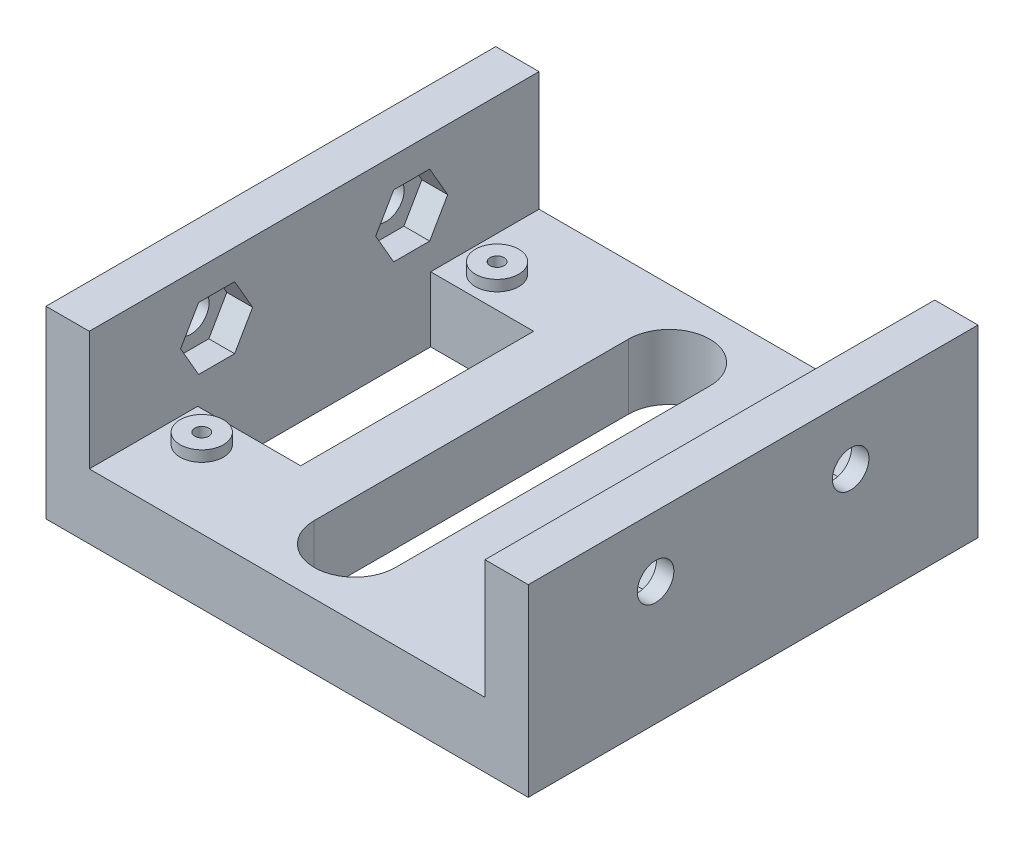
SolidWorks part; units mm, degrees
ref_plane "Front Plane" through (0, 0, 0) normal (0, 0, 1) x (1, 0, 0)
ref_plane "Top Plane" through (0, 0, 0) normal (0, 1, 0) x (1, 0, 0)
ref_plane "Right Plane" through (0, 0, 0) normal (1, 0, 0) x (0, 0, -1)
sketch "Sketch1" plane through (0, 0, 0) normal (0, 1, 0) x (1, 0, 0)
  line L9 (-44.5, 0) -> (44.5, 0)
  line L10 (-44.5, 0) -> (-44.5, 83)
  line L11 (-44.5, 83) -> (44.5, 83)
  line L12 (44.5, 0) -> (44.5, 83)
  line L13 (34.5, 0) -> (-34.5, 0) construction
  line L14 (34.5, 0) -> (34.5, 83) construction
  line L15 (34.5, 83) -> (-34.5, 83) construction
  line L16 (-34.5, 0) -> (-34.5, 83) construction
  line L21 (-30, 14.25) -> (30, 14.25) construction
  line L22 (-30, 14.25) -> (-30, 68.75) construction
  line L23 (-30, 68.75) -> (30, 68.75) construction
  line L24 (30, 14.25) -> (30, 68.75) construction
  line L27 (-7.5, 70.5) -> (-7.5, 12.5)
  line L29 (7.5, 12.5) -> (7.5, 70.5)
  circle A0 centre (30, 14.25) radius 1.3
  circle A1 centre (-30, 14.25) radius 1.3
  circle A2 centre (-30, 68.75) radius 1.3
  circle A3 centre (30, 68.75) radius 1.3
  circle A4 centre (-30, 68.75) radius 1.75 construction
  circle A6 centre (0, 70.5) radius 7.5
  circle A7 centre (0, 12.5) radius 7.5
  point P9 (0, 0)
  point P10 (0, 0)
  point P25 (0, 14.25)
  point P27 (44.5, 41.5)
  point P28 (30, 41.5)
  dimension "D7" = 2.6
  dimension "D8" = 3.5
  dimension "D1" = 83
  dimension "D2" = 69
  dimension "D3" = 10
  dimension "D4" = 15
  dimension "D5" = 5
  dimension "D6" = 5
  dimension "D9" = 60
  dimension "D10" = 54.5
extrude "Main Body" add sketch "Sketch1" along normal blind 14 contours L9 L12 L11 L10 A3 A2 A1 A0 region at (-43.283, 0, -41.5)
sketch "Sketch2" plane through (0, 14, 0) normal (0, 1, 0) x (1, 0, 0)
  line L1 (-36.5125, 0) -> (36.5125, 0)
  line L2 (-36.5125, 0) -> (-36.5125, 83)
  line L3 (-36.5125, 83) -> (36.5125, 83)
  line L4 (36.5125, 0) -> (36.5125, 83)
  line L7 (-44.5, 83) -> (44.5, 83) construction
  circle A2 centre (-30, 14.25) radius 4
  circle A3 centre (30, 14.25) radius 4
  circle A4 centre (-30, 68.75) radius 4
  circle A5 centre (30, 68.75) radius 4
  point P8 (0, 0)
  dimension "D2" = 8
  dimension "D1" = 73.025
extrude "Screw Riser" cut sketch "Sketch2" against normal blind 2
sketch "Sketch4" plane through (0, 14, 0) normal (0, 1, 0) x (1, 0, 0)
  line L0 (-44.5, 0) -> (-36.5125, 0) construction
  line L1 (-44.5, 83) -> (-36.5125, 83)
  line L2 (-44.5, 83) -> (-44.5, 0)
  line L3 (-44.5, 0) -> (-36.5125, 0)
  line L4 (-36.5125, 83) -> (-36.5125, 0)
  line L5 (36.5125, 83) -> (44.5, 83) construction
  line L6 (44.5, 0) -> (36.5125, 0)
  line L7 (44.5, 0) -> (44.5, 83)
  line L8 (44.5, 83) -> (36.5125, 83)
  line L9 (36.5125, 0) -> (36.5125, 83)
extrude "Topper Support" add sketch "Sketch4" along normal offset from surface (20 mm away) 34 up to face at (0, 0, -41.5)
sketch "Sketch6" plane through (-44.5, 0, 0) normal (-1, 0, 0) x (0, 0, 1)
  line L0 (-52.8551, 22.7547) -> (-56.1775, 28.5094)
  line L1 (-53.0842, 22.7547) -> (-56.2921, 28.3109) construction
  line L2 (-56.2921, 28.3109) -> (-62.7079, 28.3109) construction
  line L3 (-62.7079, 28.3109) -> (-65.9158, 22.7547) construction
  line L4 (-65.9158, 22.7547) -> (-62.7079, 17.1984) construction
  line L5 (-62.7079, 17.1984) -> (-56.2921, 17.1984) construction
  line L6 (-56.2921, 17.1984) -> (-53.0842, 22.7547) construction
  line L7 (-56.1775, 28.5094) -> (-62.8225, 28.5094)
  line L8 (-62.8225, 28.5094) -> (-66.1449, 22.7547)
  line L9 (-66.1449, 22.7547) -> (-62.8225, 17)
  line L10 (-62.8225, 17) -> (-56.1775, 17)
  line L11 (-56.1775, 17) -> (-52.8551, 22.7547)
  line L12 (-23.5, 22.7547) -> (-59.5, 22.7547) construction
  line L13 (-16.8551, 22.7547) -> (-20.1775, 28.5094)
  line L14 (-20.1775, 28.5094) -> (-26.8225, 28.5094)
  line L15 (-26.8225, 28.5094) -> (-30.1449, 22.7547)
  line L16 (-30.1449, 22.7547) -> (-26.8225, 17)
  line L17 (-26.8225, 17) -> (-20.1775, 17)
  line L18 (-20.1775, 17) -> (-16.8551, 22.7547)
  line L19 (0, 0) -> (-83, 0) construction
  line L20 (-83, 34) -> (0, 34) construction
  circle A0 centre (-59.5, 22.7547) radius 5.5563 construction
  circle A1 centre (-23.5, 22.7547) radius 5.7547 construction
  point P26 (-41.5, 0)
  point P27 (-41.5, 22.7547)
  dimension "D1" = 11.1125
  dimension "D3" = 36
  dimension "D4" = 17
  dimension "D2" = 0.1984
extrude "Mount Nuts" cut sketch "Sketch6" along normal offset from surface (41.275 mm away) 4.7625 from surface up to face at (-36.5125, 23, -41.5) offset beyond the face yes starting at plane "Right Plane"
sketch "Sketch5" plane through (-36.5125, 0, 0) normal (-1, 0, 0) x (0, 0, 1)
  line L0 (0, 0) -> (-83, 0) construction
  line L1 (-20.1775, 17) -> (-26.8225, 28.5094) construction
  line L4 (-59.5, 22.7547) -> (-23.5, 22.7547) construction
  circle A0 centre (-59.5, 22.7547) radius 3.175 construction
  circle A1 centre (-23.5, 22.7547) radius 3.175 construction
  circle A2 centre (-59.5, 22.7547) radius 3.3734
  circle A3 centre (-23.5, 22.7547) radius 3.3734
  circle A4 centre (-23.5, 22.7547) radius 7.9375 construction
  circle A5 centre (-59.5, 22.7547) radius 7.9375 construction
  point P2 (-23.5, 22.7547)
  point P3 (-41.5, 0)
  point P4 (-41.5, 22.7547)
  dimension "D2" = 6.35
  dimension "D5" = 15.875
  dimension "D3" = 0.1984
extrude "9/32 Mount Holes" cut sketch "Sketch5" along normal up to next
sketch "Sketch8" plane through (0, 14, 0) normal (0, 1, 0) x (1, 0, 0)
  line L17 (-7.5, 12.5) -> (-7.5, 70.5) construction
  line L33 (-36.5125, 0) -> (36.5125, 0) construction
  line L34 (-36.5125, 20) -> (36.5125, 20) construction
  line L35 (-36.5125, 20) -> (-36.5125, 63) construction
  line L36 (-36.5125, 63) -> (36.5125, 63) construction
  line L37 (36.5125, 20) -> (36.5125, 63) construction
  line L38 (36.5125, 83) -> (-36.5125, 83) construction
  line L39 (36.5125, 83) -> (36.5125, 0) construction
  line L40 (-36.5125, 0) -> (-36.5125, 83) construction
  line L42 (-36.5125, 63) -> (-17.5, 63)
  line L43 (-36.5125, 63) -> (-36.5125, 20)
  line L44 (-36.5125, 20) -> (-17.5, 20)
  line L45 (-17.5, 63) -> (-17.5, 20)
  line L47 (36.5125, 63) -> (17.5, 63)
  line L48 (36.5125, 63) -> (36.5125, 20)
  line L49 (36.5125, 20) -> (17.5, 20)
  line L50 (17.5, 63) -> (17.5, 20)
  dimension "D1" = 20
  dimension "D2" = 20
  dimension "D3" = 10
extrude "Middle Cut" cut sketch "Sketch8" against normal up to surface (14 mm away) up to face at (0, 0, -41.5)
sketch "Sketch9" plane through (36.5125, 0, 0) normal (-1, 0, 0) x (0, 0, 1)
  line L0 (-26.8225, 17) -> (-30.1449, 22.7547) construction
  line L1 (-30.1449, 22.7547) -> (-26.8225, 28.5094) construction
  line L2 (-26.8225, 28.5094) -> (-20.1775, 28.5094) construction
  line L3 (-20.1775, 28.5094) -> (-16.8551, 22.7547) construction
  line L4 (-16.8551, 22.7547) -> (-20.1775, 17) construction
  line L5 (-20.1775, 17) -> (-26.8225, 17) construction
  line L6 (-62.8225, 17) -> (-66.1449, 22.7547) construction
  line L7 (-66.1449, 22.7547) -> (-62.8225, 28.5094) construction
  line L8 (-62.8225, 28.5094) -> (-56.1775, 28.5094) construction
  line L9 (-56.1775, 28.5094) -> (-52.8551, 22.7547) construction
  line L10 (-52.8551, 22.7547) -> (-56.1775, 17) construction
  line L11 (-56.1775, 17) -> (-62.8225, 17) construction
  line L12 (-26.8225, 17) -> (-30.1449, 22.7547)
  line L13 (-30.1449, 22.7547) -> (-26.8225, 28.5094)
  line L14 (-26.8225, 28.5094) -> (-20.1775, 28.5094)
  line L15 (-20.1775, 28.5094) -> (-16.8551, 22.7547)
  line L16 (-16.8551, 22.7547) -> (-20.1775, 17)
  line L17 (-20.1775, 17) -> (-26.8225, 17)
  line L18 (-62.8225, 17) -> (-66.1449, 22.7547)
  line L19 (-66.1449, 22.7547) -> (-62.8225, 28.5094)
  line L20 (-62.8225, 28.5094) -> (-56.1775, 28.5094)
  line L21 (-56.1775, 28.5094) -> (-52.8551, 22.7547)
  line L22 (-52.8551, 22.7547) -> (-56.1775, 17)
  line L23 (-56.1775, 17) -> (-62.8225, 17)
  circle A0 centre (-59.5, 22.7547) radius 3.3734 construction
  circle A1 centre (-23.5, 22.7547) radius 3.3734 construction
  circle A2 centre (-59.5, 22.7547) radius 3.3734
  circle A3 centre (-23.5, 22.7547) radius 3.3734
extrude "Mount Nuts p2" cut sketch "Sketch9" against normal blind 4.7625 contours L23 L22 L21 L20 L19 L18 A2 | A2 | L17 L16 L15 L14 L13 L12 A3 | A3 | L18 L19 L20 L21 L22 L23 region at (36.5125, 19.9652, -28.3315) region at (36.5125, 19.9652, -64.3315) region at (36.5125, 22.7547, -59.5) region at (36.5125, 22.7547, -23.5)
extrude "9/32 Mount Holes p2" cut sketch "Sketch9<3>" against normal up to surface (7.9875 mm away) contours A2 | A3 region at (36.5125, 22.7547, -59.5) region at (36.5125, 22.7547, -23.5) up to face at (44.5, 17, -41.5)
sketch "Sketch9<3>" plane through (36.5125, 0, 0) normal (-1, 0, 0) x (0, 0, 1) same geometry as "Sketch9"
